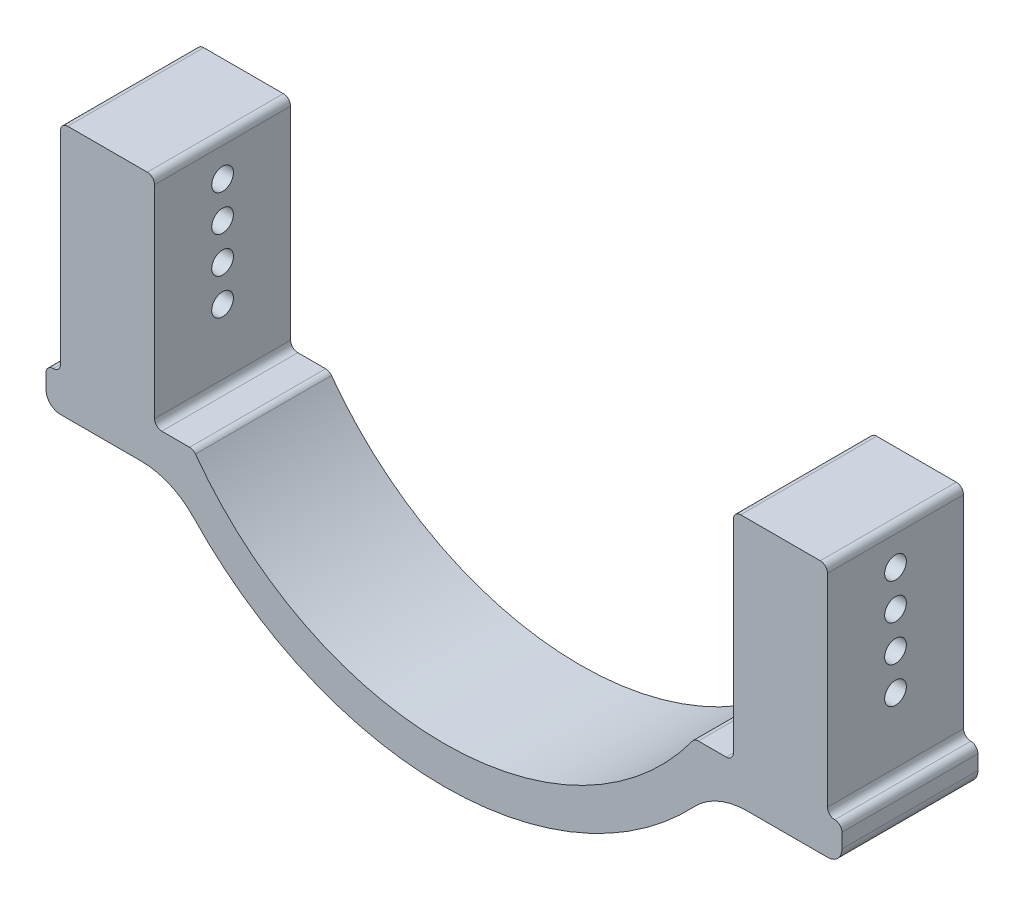
SolidWorks part; units mm, degrees
ref_plane "Front Plane" through (0, 0, 0) normal (0, 0, 1) x (1, 0, 0)
ref_plane "Top Plane" through (0, 0, 0) normal (0, 1, 0) x (1, 0, 0)
ref_plane "Right Plane" through (0, 0, 0) normal (1, 0, 0) x (0, 0, -1)
sketch "Sketch1" plane through (0, 0, 0) normal (0, 0, 1) x (1, 0, 0)
  line L0 (0, -20) -> (0, 17.3153) construction
  line L1 (53, 10) -> (40, 10)
  line L2 (53, 10) -> (53, -20)
  line L3 (53, -20) -> (55, -20)
  line L4 (40, 10) -> (40, -20)
  line L5 (40, -20) -> (34.641, -20)
  line L6 (-53, 10) -> (-40, 10)
  line L7 (-40, 10) -> (-40, -20)
  line L8 (-53, 10) -> (-53, -20)
  line L9 (-53, -20) -> (-55, -20)
  line L10 (-40, -20) -> (-34.641, -20)
  line L11 (55, -20) -> (55, -23)
  line L12 (53, -25) -> (41.8728, -25)
  line L13 (-55, -20) -> (-55, -23)
  line L14 (-53, -25) -> (-41.8728, -25)
  arc A0 (34.6092, -28.1268) -> (-34.6092, -28.1268) centre (0, 4.6221) cw
  circle A1 centre (0, 0) radius 40 construction
  arc A2 (34.641, -20) -> (-34.641, -20) centre (0, 4.6221) cw
  arc A4 (-41.8728, -25) -> (-34.6092, -28.1268) centre (-41.8728, -35) cw
  arc A5 (41.8728, -25) -> (34.6092, -28.1268) centre (41.8728, -35) ccw
  arc A6 (-55, -23) -> (-53, -25) centre (-53, -23) ccw
  arc A7 (55, -23) -> (53, -25) centre (53, -23) cw
  point P28 (-37.3205, -25)
  point P31 (37.3205, -25)
  point P34 (-55, -25)
  point P37 (55, -25)
  dimension "D3" = 42.5
  dimension "D4" = 10
  dimension "D5" = 2
  dimension "D1" = 17.6795
  dimension "D2" = 5
extrude "Boss-Extrude1" add sketch "Sketch1" along normal blind 18.8
sketch "Sketch2" plane through (-53, 0, 0) normal (-1, 0, 0) x (0, 0, 1)
  line L0 (9.4, 10) -> (9.4, -20) construction
  line L1 (18.8, 10) -> (0, 10) construction
  line L2 (18.8, -20) -> (0, -20) construction
  circle A0 centre (9.4, -5) radius 1.5
  circle A1 centre (9.4, 5) radius 1.5
  circle A2 centre (9.4, 0) radius 1.5
  circle A3 centre (9.4, -10) radius 1.5
  dimension "D1" = 3
  dimension "D2" = 3
  dimension "D3" = 3
  dimension "D4" = 3
  dimension "D6" = 5
  dimension "D7" = 5
  dimension "D8" = 10
  dimension "D5" = 5
extrude "Cut-Extrude1" cut sketch "Sketch2" against normal blind 168.8
fillet "Fillet1" radius 1 4 edges at (-40, -20, 9.4) (-34.641, -20, 9.4) (40, -20, 9.4) (34.641, -20, 9.4)
fillet "Fillet2" radius 1 8 edges at (-55, -20, 9.4) (-53, -20, 9.4) (-40, 10, 9.4) (-53, 10, 9.4) (55, -20, 9.4) (53, -20, 9.4) (53, 10, 9.4) (40, 10, 9.4)
